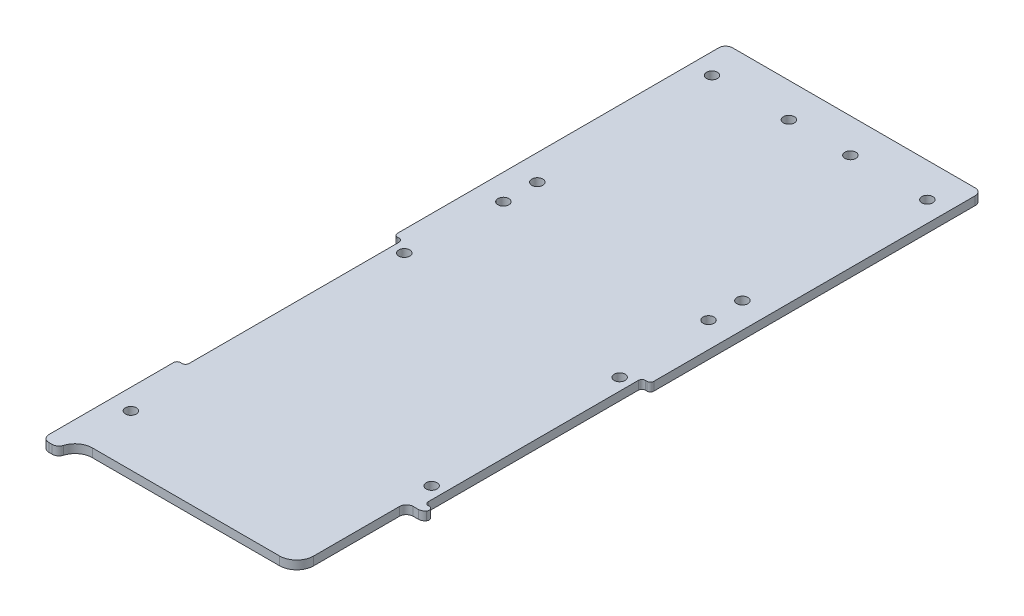
SolidWorks part; units mm, degrees
ref_plane "Front Plane" through (0, 0, 0) normal (0, 0, 1) x (1, 0, 0)
ref_plane "Top Plane" through (0, 0, 0) normal (0, 1, 0) x (1, 0, 0)
ref_plane "Right Plane" through (0, 0, 0) normal (1, 0, 0) x (0, 0, -1)
sketch "Sketch1" plane through (0, 0, 0) normal (0, 1, 0) x (1, 0, 0)
  line L0 (-39.9997, 0) -> (-39.9997, 114.3) construction
  line L1 (-47.625, 127) -> (47.625, 127)
  line L2 (-47.625, 127) -> (-47.625, -127)
  line L3 (-47.625, -127) -> (47.625, -127)
  line L4 (47.625, 127) -> (47.625, -127)
  line L5 (-47.625, 127) -> (47.625, -127) construction
  line L6 (-47.625, -127) -> (47.625, 127) construction
  line L7 (0, 0) -> (0, 127) construction
  line L8 (-39.9997, 0) -> (-39.9997, -101.6) construction
  line L9 (-39.9997, 0) -> (0, 0) construction
  line L10 (-41.275, -127) -> (-41.275, -120.65)
  line L11 (-41.275, -120.65) -> (41.275, -120.65)
  line L12 (41.275, -120.65) -> (41.275, -127)
  line L13 (-39.9997, 114.3) -> (-11.4247, 114.3) construction
  line L14 (39.9997, 114.3) -> (11.4247, 114.3) construction
  circle A0 centre (-39.9997, 114.3) radius 2.032
  circle A1 centre (-39.9997, 0) radius 2.032
  circle A2 centre (-39.9997, -101.6) radius 2.032
  circle A3 centre (39.9997, -101.6) radius 2.032
  circle A4 centre (39.9997, 0) radius 2.032
  circle A5 centre (39.9997, 114.3) radius 2.032
  circle A6 centre (-11.4247, 114.3) radius 2.032
  circle A7 centre (11.4247, 114.3) radius 2.032
  circle A8 centre (-39.9997, -69.85) radius 2.032
  circle A9 centre (39.9997, -69.85) radius 2.032
  point P0 (0, 0)
  dimension "D4" = 4.064
  dimension "D10" = 28.575
  dimension "D1" = 95.25
  dimension "D2" = 254
  dimension "D3" = 7.6253
  dimension "D5" = 12.7
  dimension "D6" = 25.4
  dimension "D7" = 6.35
  dimension "D8" = 6.35
  dimension "D9" = 6.35
  dimension "D11" = 69.85
extrude "Boss-Extrude1" add sketch "Sketch1" along normal blind 3.175 contours L4 L1 L2 L3 A4 A0 A1 A2 A3 A5 | A8 | A3 region at (0, 0, -2.6944) region at (39.9997, 0, 101.6) region at (-39.9997, 0, 69.85)
fillet "Fillet1" radius 2.54 4 edges at (-47.625, 1.5875, -127) (47.625, 1.5875, -127) (47.625, 1.5875, 127) (-47.625, 1.5875, 127)
fillet "Fillet2" radius 2.54 2 edges at (41.275, 1.5875, 127) (-41.275, 1.5875, 127)
fillet "Fillet3" radius 6.35 2 edges at (41.275, 1.5875, 120.65) (-41.275, 1.5875, 120.65)
sketch "Sketch2" plane through (0, 0, 0) normal (0, -1, 0) x (1, 0, 0)
  line L1 (43.815, 127) -> (45.085, 127) construction
  line L2 (40.6451, 123.5787) -> (40.6451, 79.8881)
  line L3 (40.6451, 79.8881) -> (47.625, 79.8881)
  line L11 (47.625, -124.46) -> (47.625, 124.46) construction
  line L12 (43.815, 127) -> (45.085, 127)
  line L13 (47.625, 79.8881) -> (47.625, 124.46)
  arc A0 (35.2956, 120.65) -> (41.3809, 125.1857) centre (35.2956, 127) ccw construction
  arc A1 (43.815, 127) -> (41.3809, 125.1857) centre (43.815, 124.46) ccw construction
  arc A2 (47.625, 124.46) -> (45.085, 127) centre (45.085, 124.46) ccw construction
  arc A3 (40.6451, 123.5787) -> (41.3809, 125.1857) centre (35.2956, 127) ccw
  arc A4 (43.815, 127) -> (41.3809, 125.1857) centre (43.815, 124.46) ccw
  arc A5 (47.625, 124.46) -> (45.085, 127) centre (45.085, 124.46) ccw
  dimension "D2" = 47.1119
  dimension "D1" = 6.9799
extrude "Cut-Extrude1" cut sketch "Sketch2" against normal through all
fillet "Fillet4" radius 6.35 1 edges at (40.6451, 1.5875, 123.5787)
fillet "Fillet5" radius 2.54 2 edges at (47.625, 1.5875, 79.8881) (40.6451, 1.5875, 79.8881)
sketch "Sketch3" plane through (0, 0, 0) normal (0, -1, 0) x (1, 0, 0)
  line L0 (-36.2991, -49.7791) -> (-39.9059, -49.7791) construction
  line L1 (-40.4139, -49.276) -> (-40.4139, -45.7043) construction
  line L2 (-35.7911, -45.7043) -> (-35.7911, -49.276) construction
  line L3 (-39.9059, -45.2013) -> (-36.2991, -45.2013) construction
  line L4 (-36.2991, -37.2027) -> (-39.9059, -37.2027) construction
  line L5 (-35.7911, -33.1279) -> (-35.7911, -36.6996) construction
  line L6 (-40.4139, -36.6996) -> (-40.4139, -33.1279) construction
  line L7 (-39.9059, -32.6249) -> (-36.2991, -32.6249) construction
  line L8 (36.2941, -32.6249) -> (39.9009, -32.6249) construction
  line L9 (40.4089, -33.1279) -> (40.4089, -36.6996) construction
  line L10 (39.9009, -37.2027) -> (36.2941, -37.2027) construction
  line L11 (35.7861, -36.6996) -> (35.7861, -33.1279) construction
  line L12 (36.2941, -45.2013) -> (39.9009, -45.2013) construction
  line L13 (35.7861, -49.276) -> (35.7861, -45.7043) construction
  line L14 (40.4089, -45.7043) -> (40.4089, -49.276) construction
  line L15 (39.9009, -49.7791) -> (36.2941, -49.7791) construction
  line L16 (-36.2991, -49.7791) -> (-39.9059, -49.7791)
  line L17 (-40.4139, -49.276) -> (-40.4139, -45.7043)
  line L18 (-35.7911, -45.7043) -> (-35.7911, -49.276)
  line L19 (-39.9059, -45.2013) -> (-36.2991, -45.2013)
  line L20 (-36.2991, -37.2027) -> (-39.9059, -37.2027)
  line L21 (-35.7911, -33.1279) -> (-35.7911, -36.6996)
  line L22 (-40.4139, -36.6996) -> (-40.4139, -33.1279)
  line L23 (-39.9059, -32.6249) -> (-36.2991, -32.6249)
  line L24 (36.2941, -32.6249) -> (39.9009, -32.6249)
  line L25 (40.4089, -33.1279) -> (40.4089, -36.6996)
  line L26 (39.9009, -37.2027) -> (36.2941, -37.2027)
  line L27 (35.7861, -36.6996) -> (35.7861, -33.1279)
  line L28 (36.2941, -45.2013) -> (39.9009, -45.2013)
  line L29 (35.7861, -49.276) -> (35.7861, -45.7043)
  line L30 (40.4089, -45.7043) -> (40.4089, -49.276)
  line L31 (39.9009, -49.7791) -> (36.2941, -49.7791)
  line L32 (-47.625, -25.836) -> (47.625, -25.836)
  line L33 (-47.625, -124.46) -> (-47.625, 124.46) construction
  line L34 (47.625, -124.46) -> (47.625, 77.3481) construction
  line L35 (0, -25.836) -> (0, -56.0686) construction
  line L1362 (-40.4139, -34.9138) -> (-35.7911, -34.9138)
  line L1857 (-38.1025, -32.6249) -> (-38.1025, -37.2027)
  line L1858 (-38.1025, -45.2013) -> (-38.1025, -49.7791)
  line L1859 (-40.4139, -47.4902) -> (-35.7911, -47.4902)
  circle A0 centre (-38.1025, -34.9138) radius 2.032
  circle A1 centre (-38.1025, -47.4902) radius 2.032
  circle A2 centre (38.1025, -47.4902) radius 2.032
  circle A3 centre (38.1025, -34.9138) radius 2.032
  ellipse E0 centre (-39.9059, -45.7043) end of major axis (-39.3979, -45.7043) minor radius 0.5031 (-39.9059, -45.2013) -> (-40.4139, -45.7043) ccw construction
  ellipse E1 centre (-39.9059, -49.276) end of major axis (-39.3979, -49.276) minor radius 0.5031 (-40.4139, -49.276) -> (-39.9059, -49.7791) ccw construction
  ellipse E6 centre (-36.2991, -49.276) end of major axis (-35.7911, -49.276) minor radius 0.5031 (-36.2991, -49.7791) -> (-35.7911, -49.276) ccw construction
  ellipse E7 centre (-36.2991, -45.7043) end of major axis (-35.7911, -45.7043) minor radius 0.5031 (-35.7911, -45.7043) -> (-36.2991, -45.2013) ccw construction
  ellipse E8 centre (-39.9059, -36.6996) end of major axis (-39.3979, -36.6996) minor radius 0.5031 (-40.4139, -36.6996) -> (-39.9059, -37.2027) ccw construction
  ellipse E9 centre (-36.2991, -36.6996) end of major axis (-35.7911, -36.6996) minor radius 0.5031 (-36.2991, -37.2027) -> (-35.7911, -36.6996) ccw construction
  ellipse E10 centre (-36.2991, -33.1279) end of major axis (-35.7911, -33.1279) minor radius 0.5031 (-35.7911, -33.1279) -> (-36.2991, -32.6249) ccw construction
  ellipse E11 centre (-39.9059, -33.1279) end of major axis (-39.3979, -33.1279) minor radius 0.5031 (-39.9059, -32.6249) -> (-40.4139, -33.1279) ccw construction
  ellipse E12 centre (39.9009, -33.1279) end of major axis (40.4089, -33.1279) minor radius 0.5031 (40.4089, -33.1279) -> (39.9009, -32.6249) ccw construction
  ellipse E13 centre (36.2941, -33.1279) end of major axis (36.8021, -33.1279) minor radius 0.5031 (36.2941, -32.6249) -> (35.7861, -33.1279) ccw construction
  ellipse E14 centre (39.9009, -36.6996) end of major axis (40.4089, -36.6996) minor radius 0.5031 (39.9009, -37.2027) -> (40.4089, -36.6996) ccw construction
  ellipse E15 centre (36.2941, -36.6996) end of major axis (36.8021, -36.6996) minor radius 0.5031 (35.7861, -36.6996) -> (36.2941, -37.2027) ccw construction
  ellipse E16 centre (36.2941, -45.7043) end of major axis (36.8021, -45.7043) minor radius 0.5031 (36.2941, -45.2013) -> (35.7861, -45.7043) ccw construction
  ellipse E17 centre (36.2941, -49.276) end of major axis (36.8021, -49.276) minor radius 0.5031 (35.7861, -49.276) -> (36.2941, -49.7791) ccw construction
  ellipse E18 centre (39.9009, -45.7043) end of major axis (40.4089, -45.7043) minor radius 0.5031 (40.4089, -45.7043) -> (39.9009, -45.2013) ccw construction
  ellipse E19 centre (39.9009, -49.276) end of major axis (40.4089, -49.276) minor radius 0.5031 (39.9009, -49.7791) -> (40.4089, -49.276) ccw construction
  ellipse E20 centre (-39.9059, -45.7043) end of major axis (-39.3979, -45.7043) minor radius 0.5031 (-39.9059, -45.2013) -> (-40.4139, -45.7043) ccw
  ellipse E21 centre (-39.9059, -49.276) end of major axis (-39.3979, -49.276) minor radius 0.5031 (-40.4139, -49.276) -> (-39.9059, -49.7791) ccw
  ellipse E22 centre (-36.2991, -49.276) end of major axis (-35.7911, -49.276) minor radius 0.5031 (-36.2991, -49.7791) -> (-35.7911, -49.276) ccw
  ellipse E23 centre (-36.2991, -45.7043) end of major axis (-35.7911, -45.7043) minor radius 0.5031 (-35.7911, -45.7043) -> (-36.2991, -45.2013) ccw
  ellipse E24 centre (-39.9059, -36.6996) end of major axis (-39.3979, -36.6996) minor radius 0.5031 (-40.4139, -36.6996) -> (-39.9059, -37.2027) ccw
  ellipse E25 centre (-36.2991, -36.6996) end of major axis (-35.7911, -36.6996) minor radius 0.5031 (-36.2991, -37.2027) -> (-35.7911, -36.6996) ccw
  ellipse E26 centre (-36.2991, -33.1279) end of major axis (-35.7911, -33.1279) minor radius 0.5031 (-35.7911, -33.1279) -> (-36.2991, -32.6249) ccw
  ellipse E27 centre (-39.9059, -33.1279) end of major axis (-39.3979, -33.1279) minor radius 0.5031 (-39.9059, -32.6249) -> (-40.4139, -33.1279) ccw
  ellipse E28 centre (39.9009, -33.1279) end of major axis (40.4089, -33.1279) minor radius 0.5031 (40.4089, -33.1279) -> (39.9009, -32.6249) ccw
  ellipse E29 centre (36.2941, -33.1279) end of major axis (36.8021, -33.1279) minor radius 0.5031 (36.2941, -32.6249) -> (35.7861, -33.1279) ccw
  ellipse E30 centre (39.9009, -36.6996) end of major axis (40.4089, -36.6996) minor radius 0.5031 (39.9009, -37.2027) -> (40.4089, -36.6996) ccw
  ellipse E31 centre (36.2941, -36.6996) end of major axis (36.8021, -36.6996) minor radius 0.5031 (35.7861, -36.6996) -> (36.2941, -37.2027) ccw
  ellipse E32 centre (36.2941, -45.7043) end of major axis (36.8021, -45.7043) minor radius 0.5031 (36.2941, -45.2013) -> (35.7861, -45.7043) ccw
  ellipse E33 centre (36.2941, -49.276) end of major axis (36.8021, -49.276) minor radius 0.5031 (35.7861, -49.276) -> (36.2941, -49.7791) ccw
  ellipse E34 centre (39.9009, -45.7043) end of major axis (40.4089, -45.7043) minor radius 0.5031 (40.4089, -45.7043) -> (39.9009, -45.2013) ccw
  ellipse E35 centre (39.9009, -49.276) end of major axis (40.4089, -49.276) minor radius 0.5031 (39.9009, -49.7791) -> (40.4089, -49.276) ccw
  dimension "D2" = 4.064
extrude "Cut-Extrude2" cut sketch "Sketch3" against normal through all contours A0 | A1 | A2 | A3
sketch "Sketch4" plane through (0, 3.175, 0) normal (0, 1, 0) x (1, 0, 0)
  line L11 (-47.625, 124.46) -> (-47.625, -124.46) construction
  line L12 (-47.625, -76.835) -> (-44.45, -76.835)
  line L13 (-47.625, -76.835) -> (-47.625, 3.81)
  line L15 (-47.625, 3.81) -> (-44.45, 3.81)
  line L16 (-44.45, -76.835) -> (-44.45, 3.81)
  line L17 (47.625, 124.46) -> (47.625, -77.3481) construction
  line L18 (47.625, -76.835) -> (44.45, -76.835)
  line L19 (47.625, -76.835) -> (47.625, 3.81)
  line L20 (47.625, 3.81) -> (44.45, 3.81)
  line L45 (44.45, -76.835) -> (44.45, 3.81)
  line L47 (43.1851, -79.8881) -> (45.085, -79.8881) construction
  dimension "D1" = 3.175
  dimension "D2" = 80.645
  dimension "D3" = 3.0531
extrude "Cut-Extrude3" cut sketch "Sketch4" against normal through all and the other way through all
fillet "Fillet6" radius 1.27 8 edges at (-44.45, 1.5875, -3.81) (-47.625, 1.5875, -3.81) (-47.625, 1.5875, 76.835) (-44.45, 1.5875, 76.835) (44.45, 1.5875, 76.835) (47.625, 1.5875, 76.835) (44.45, 1.5875, -3.81) (47.625, 1.5875, -3.81)
